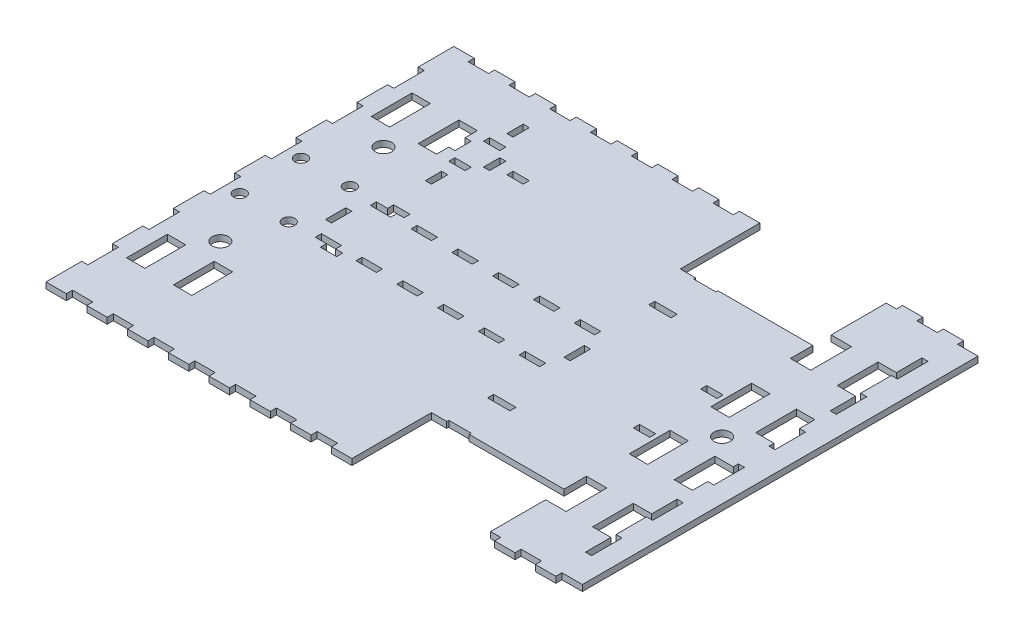
SolidWorks part; units mm, degrees
ref_plane "Front Plane" through (0, 0, 0) normal (0, 0, 1) x (1, 0, 0)
ref_plane "Top Plane" through (0, 0, 0) normal (0, 1, 0) x (1, 0, 0)
ref_plane "Right Plane" through (0, 0, 0) normal (1, 0, 0) x (0, 0, -1)
sketch "Sketch3" plane through (0, 0, 0) normal (0, 1, 0) x (1, 0, 0)
  line L0 (0, 0) -> (-300, 0) construction
  line L1 (-300, -97) -> (-300, 97)
  line L2 (-290, 100) -> (-300, 100)
  line L3 (-290, 97) -> (-290, 100)
  line L4 (-280, 97) -> (-290, 97)
  line L5 (-300, 100) -> (-300, 97)
  line L6 (-270, 100) -> (-280, 100)
  line L7 (-270, 97) -> (-270, 100)
  line L8 (-260, 97) -> (-270, 97)
  line L9 (-280, 100) -> (-280, 97)
  line L10 (-250, 100) -> (-260, 100)
  line L11 (-250, 97) -> (-250, 100)
  line L12 (-240, 97) -> (-250, 97)
  line L13 (-260, 100) -> (-260, 97)
  line L14 (-150, -100) -> (-150, 100) construction
  line L15 (-230, 100) -> (-240, 100)
  line L16 (-230, 97) -> (-230, 100)
  line L17 (-220, 97) -> (-230, 97)
  line L18 (-240, 100) -> (-240, 97)
  line L19 (-210, 100) -> (-220, 100)
  line L20 (-210, 97) -> (-210, 100)
  line L21 (-200, 97) -> (-210, 97)
  line L22 (-40, 97) -> (-40, -97)
  line L23 (-50, 37.5) -> (-53, 37.5)
  line L24 (-50, 7.5) -> (-53, 7.5)
  line L25 (-50, -45.947) -> (-50, 45.947) construction
  line L26 (-247, 37.5) -> (-250, 37.5) construction
  line L27 (-247, 7.5) -> (-250, 7.5) construction
  line L28 (-247, 48.5) -> (-247, -48.5) construction
  line L29 (-247, 48.5) -> (-223, 48.5) construction
  line L30 (-223, 48.5) -> (-223, -48.5) construction
  line L31 (-210, 15) -> (-90, 15) construction
  line L32 (-90, 15) -> (-90, 5) construction
  line L33 (-50, 7.5) -> (-50, 22.5)
  line L34 (-220, 100) -> (-220, 97)
  line L35 (-190, 100) -> (-200, 100)
  line L36 (-190, 97) -> (-190, 100)
  line L37 (-180, 97) -> (-190, 97)
  line L38 (-200, 100) -> (-200, 97)
  line L39 (-170, 100) -> (-180, 100)
  line L40 (-170, 97) -> (-170, 100)
  line L41 (-160, 97) -> (-170, 97)
  line L42 (-180, 100) -> (-180, 97)
  line L43 (-150, 100) -> (-160, 100)
  line L44 (-150, 97) -> (-150, 100)
  line L45 (-140, 97) -> (-150, 97)
  line L46 (-160, 100) -> (-160, 97)
  line L47 (-130, 100) -> (-140, 100)
  line L48 (-130, 97) -> (-130, 100)
  line L49 (-120, 97) -> (-130, 97)
  line L50 (-140, 100) -> (-140, 97)
  line L51 (-110, 100) -> (-120, 100)
  line L52 (-110, 97) -> (-110, 100)
  line L53 (-100, 97) -> (-110, 97)
  line L54 (-120, 100) -> (-120, 97)
  line L55 (-90, 100) -> (-100, 100)
  line L56 (-90, 97) -> (-90, 100)
  line L57 (-80, 97) -> (-90, 97)
  line L58 (-100, 100) -> (-100, 97)
  line L59 (-70, 100) -> (-80, 100)
  line L60 (-70, 97) -> (-70, 100)
  line L61 (-60, 97) -> (-70, 97)
  line L62 (-80, 100) -> (-80, 97)
  line L63 (-50, 100) -> (-60, 100)
  line L64 (-50, 97) -> (-50, 100)
  line L65 (-40, 97) -> (-50, 97)
  line L66 (-60, 100) -> (-60, 97)
  line L67 (-50, 22.5) -> (-53, 22.5)
  line L68 (-210, -15) -> (-90, -15) construction
  line L69 (-53, 7.5) -> (-53, 22.5)
  line L70 (-50, 37.5) -> (-50, 52.5)
  line L71 (-50, 52.5) -> (-53, 52.5)
  line L72 (-53, 37.5) -> (-53, 52.5)
  line L73 (-50, 67.5) -> (-53, 67.5)
  line L74 (-50, 67.5) -> (-50, 82.5)
  line L75 (-50, 82.5) -> (-53, 82.5)
  line L76 (-60, -100) -> (-60, -97)
  line L77 (-40, -97) -> (-50, -97)
  line L78 (-50, -97) -> (-50, -100)
  line L79 (-50, -100) -> (-60, -100)
  line L80 (-80, -100) -> (-80, -97)
  line L81 (-60, -97) -> (-70, -97)
  line L82 (-70, -97) -> (-70, -100)
  line L83 (-70, -100) -> (-80, -100)
  line L84 (-100, -100) -> (-100, -97)
  line L85 (-80, -97) -> (-90, -97)
  line L86 (-90, -97) -> (-90, -100)
  line L87 (-90, -100) -> (-100, -100)
  line L88 (-120, -100) -> (-120, -97)
  line L89 (-100, -97) -> (-110, -97)
  line L90 (-110, -97) -> (-110, -100)
  line L91 (-110, -100) -> (-120, -100)
  line L92 (-140, -100) -> (-140, -97)
  line L93 (-120, -97) -> (-130, -97)
  line L94 (-130, -97) -> (-130, -100)
  line L95 (-130, -100) -> (-140, -100)
  line L96 (-160, -100) -> (-160, -97)
  line L97 (-140, -97) -> (-150, -97)
  line L98 (-150, -97) -> (-150, -100)
  line L99 (-150, -100) -> (-160, -100)
  line L100 (-180, -100) -> (-180, -97)
  line L101 (-160, -97) -> (-170, -97)
  line L102 (-170, -97) -> (-170, -100)
  line L103 (-170, -100) -> (-180, -100)
  line L104 (-200, -100) -> (-200, -97)
  line L105 (-180, -97) -> (-190, -97)
  line L106 (-190, -97) -> (-190, -100)
  line L107 (-190, -100) -> (-200, -100)
  line L108 (-247, -48.5) -> (-223, -48.5) construction
  line L109 (-247, 7.5) -> (-247, 22.5) construction
  line L110 (-220, -100) -> (-220, -97)
  line L111 (-53, 67.5) -> (-53, 82.5)
  line L112 (-53, -67.5) -> (-53, -82.5)
  line L113 (-50, -82.5) -> (-53, -82.5)
  line L114 (-200, -97) -> (-210, -97)
  line L115 (-210, -97) -> (-210, -100)
  line L116 (-210, -100) -> (-220, -100)
  line L117 (-240, -100) -> (-240, -97)
  line L118 (-220, -97) -> (-230, -97)
  line L119 (-230, -97) -> (-230, -100)
  line L120 (-230, -100) -> (-240, -100)
  line L121 (-50, -67.5) -> (-50, -82.5)
  line L122 (-260, -100) -> (-260, -97)
  line L123 (-240, -97) -> (-250, -97)
  line L124 (-250, -97) -> (-250, -100)
  line L125 (-250, -100) -> (-260, -100)
  line L126 (-280, -100) -> (-280, -97)
  line L127 (-260, -97) -> (-270, -97)
  line L128 (-270, -97) -> (-270, -100)
  line L129 (-270, -100) -> (-280, -100)
  line L130 (-300, -100) -> (-300, -97)
  line L131 (-210, 15) -> (-210, -15) construction
  line L132 (-253, -15) -> (-243, -15)
  line L133 (-233, -15) -> (-223, -15)
  line L188 (-247, 22.5) -> (-250, 22.5) construction
  line L189 (-250, 7.5) -> (-250, 22.5) construction
  line L190 (-247, 37.5) -> (-247, 52.5) construction
  line L191 (-247, 52.5) -> (-250, 52.5) construction
  line L192 (-250, 37.5) -> (-250, 52.5) construction
  line L193 (-247, 67.5) -> (-250, 67.5) construction
  line L194 (-247, 67.5) -> (-247, 82.5) construction
  line L195 (-247, 82.5) -> (-250, 82.5) construction
  line L196 (-250, 67.5) -> (-250, 82.5) construction
  line L197 (-250, -67.5) -> (-250, -82.5) construction
  line L198 (-247, -82.5) -> (-250, -82.5) construction
  line L199 (-247, -67.5) -> (-247, -82.5) construction
  line L200 (-247, -67.5) -> (-250, -67.5) construction
  line L201 (-250, -37.5) -> (-250, -52.5) construction
  line L202 (-247, -52.5) -> (-250, -52.5) construction
  line L203 (-247, -37.5) -> (-247, -52.5) construction
  line L204 (-250, -7.5) -> (-250, -22.5) construction
  line L205 (-247, -22.5) -> (-250, -22.5) construction
  line L206 (-247, -7.5) -> (-247, -22.5) construction
  line L207 (-247, -7.5) -> (-250, -7.5) construction
  line L208 (-247, -37.5) -> (-250, -37.5) construction
  line L209 (-50, -67.5) -> (-53, -67.5)
  line L210 (-53, -37.5) -> (-53, -52.5)
  line L211 (-50, -52.5) -> (-53, -52.5)
  line L212 (-50, -37.5) -> (-50, -52.5)
  line L213 (-53, -7.5) -> (-53, -22.5)
  line L214 (-50, -22.5) -> (-53, -22.5)
  line L215 (-50, -7.5) -> (-50, -22.5)
  line L216 (-50, -7.5) -> (-53, -7.5)
  line L217 (-50, -37.5) -> (-53, -37.5)
  line L218 (-210, 0) -> (-258, 0)
  line L219 (-258, -5) -> (-255, -5)
  line L220 (-163, 15) -> (-173, 15)
  line L221 (-243, -12) -> (-243, -15)
  line L222 (-143, 15) -> (-143, 12)
  line L223 (-173, -15) -> (-173, -12)
  line L224 (-163, -15) -> (-173, -15)
  line L225 (-183, 12) -> (-183, 15)
  line L226 (-153, 15) -> (-153, 12)
  line L227 (-163, -12) -> (-163, -15)
  line L228 (-243, -12) -> (-253, -12)
  line L229 (-193, -15) -> (-193, -12)
  line L230 (-258, 5) -> (-255, 5)
  line L231 (-280, -97) -> (-290, -97)
  line L232 (-290, -97) -> (-290, -100)
  line L233 (-290, -100) -> (-300, -100)
  line L234 (-143, 15) -> (-153, 15)
  line L235 (-203, -12) -> (-213, -12)
  line L236 (-213, -15) -> (-213, -12)
  line L237 (-233, -15) -> (-233, -12)
  line L238 (-138, 5) -> (-141, 5)
  line L239 (-243, 12) -> (-243, 15)
  line L240 (-223, 12) -> (-223, 15)
  line L241 (-203, 12) -> (-213, 12)
  line L242 (-153, -15) -> (-153, -12)
  line L243 (-253, 15) -> (-253, 12)
  line L244 (-163, 12) -> (-163, 15)
  line L245 (-141, 5) -> (-141, -5)
  line L246 (-143, -15) -> (-143, -12)
  line L247 (-223, -12) -> (-233, -12)
  line L248 (-258, 15) -> (-258, -15) construction
  line L249 (-233, 15) -> (-233, 12)
  line L250 (-223, 15) -> (-233, 15)
  line L251 (-138, -5) -> (-141, -5)
  line L252 (-183, -15) -> (-193, -15)
  line L253 (-203, 15) -> (-213, 15)
  line L254 (-138, 5) -> (-138, -5)
  line L255 (-258, -15) -> (-138, -15) construction
  line L256 (-255, 5) -> (-255, -5)
  line L257 (-258, 5) -> (-258, -5)
  line L258 (-258, 15) -> (-138, 15) construction
  line L259 (-193, 15) -> (-193, 12)
  line L260 (-163, 12) -> (-173, 12)
  line L261 (-203, -15) -> (-213, -15)
  line L262 (-243, 12) -> (-253, 12)
  line L263 (-183, 15) -> (-193, 15)
  line L264 (-143, 12) -> (-153, 12)
  line L265 (-243, 15) -> (-253, 15)
  line L266 (-213, 15) -> (-213, 12)
  line L267 (-173, 15) -> (-173, 12)
  line L268 (-223, -12) -> (-223, -15)
  line L269 (-143, -12) -> (-153, -12)
  line L270 (-143, -15) -> (-153, -15)
  line L271 (-183, -12) -> (-193, -12)
  line L272 (-203, -12) -> (-203, -15)
  line L273 (-203, 12) -> (-203, 15)
  line L274 (-183, -12) -> (-183, -15)
  line L275 (-253, -15) -> (-253, -12)
  line L276 (-223, 12) -> (-233, 12)
  line L277 (-183, 12) -> (-193, 12)
  line L278 (-163, -12) -> (-173, -12)
  circle A0 centre (-290, 15) radius 3
  circle A1 centre (-266, 15) radius 3
  circle A2 centre (-266, -15) radius 3
  circle A3 centre (-290, -15) radius 3
  point P31 (-250, 36)
  point P80 (-91.5, 0)
  point P82 (-150, 0)
  point P126 (-223, 0)
  point P128 (-250, 18)
  point P129 (-50, 0)
  point P150 (-150, -15)
  point P151 (-150, 15)
  point P183 (-208.5, 0)
  point P212 (-223, 18)
  point P218 (-223, 36)
  point P235 (-198, -15)
  point P236 (-198, 15)
  dimension "D17" = 6
  dimension "D18" = 6
  dimension "D1" = 300
  dimension "D4" = 7.5
  dimension "D5" = 100
  dimension "D6" = 97
  dimension "D7" = 15
  dimension "D8" = 97
  dimension "D9" = 3
  dimension "D10" = 3
  dimension "D11" = 48.5
  dimension "D12" = 24
  dimension "D13" = 60
  dimension "D14" = 15
  dimension "D15" = 24
  dimension "D16" = 15
  dimension "D19" = 194
  dimension "D20" = 10
  dimension "D21" = 3
  dimension "D22" = 7.5
  dimension "D23" = 15
  dimension "D24" = 3
  dimension "D25" = 3
  dimension "D26" = 48
  dimension "D31" = 10
  dimension "D36" = 3
extrude "Boss-Extrude1" add sketch "Sketch3" along normal blind 3 contours L1 L116 L115 L107 L106 L83 L82 L79 L95 L98 L99 L91 L90 L86 region at (-170.2364, 0, 0)
sketch "Sketch5" plane through (0, 3, 0) normal (0, 1, 0) x (1, 0, 0)
  line L0 (-85, 0) -> (-85, 61) construction
  line L1 (-137, -60) -> (-137, -41)
  line L2 (-85, 61) -> (-131.5, 61)
  line L3 (-85, 61) -> (-85, 97)
  line L4 (-85, 97) -> (-150, 97)
  line L5 (-150, 61) -> (-150, 97)
  line L7 (-110, 100) -> (-120, 100) construction
  line L8 (-85, 0) -> (-300, 0) construction
  line L9 (-300, 100) -> (-300, -100) construction
  line L10 (-150, -61) -> (-150, -97)
  line L11 (-85, -97) -> (-150, -97)
  line L12 (-85, -61) -> (-85, -97)
  line L13 (-85, -61) -> (-131.5, -61)
  line L14 (-117.5, -61) -> (-117.5, -41) construction
  line L15 (-117.5, -41) -> (-131.5, -41) construction
  line L16 (-131.5, -41) -> (-131.5, -38)
  line L17 (-131.5, -38) -> (-142.5, -38)
  line L18 (-142.5, -38) -> (-142.5, -41)
  line L19 (-142.5, -41) -> (-131.5, -41)
  line L20 (-131.5, -61) -> (-131.5, -60)
  line L21 (-131.5, -60) -> (-142.5, -60)
  line L22 (-142.5, -60) -> (-142.5, -61)
  line L23 (-142.5, -61) -> (-150, -61)
  line L24 (-117.5, 41) -> (-131.5, 41) construction
  line L25 (-117.5, 61) -> (-117.5, 41) construction
  line L26 (-142.5, 60) -> (-142.5, 61)
  line L27 (-131.5, 60) -> (-142.5, 60)
  line L28 (-131.5, 61) -> (-131.5, 60)
  line L29 (-142.5, 41) -> (-131.5, 41)
  line L30 (-142.5, 38) -> (-142.5, 41)
  line L31 (-131.5, 38) -> (-142.5, 38)
  line L32 (-131.5, 41) -> (-131.5, 38)
  line L33 (-142.5, 61) -> (-150, 61)
  dimension "D1" = 19
  dimension "D2" = 36
  dimension "D3" = 3
  dimension "D5" = 14
  dimension "D6" = 3
  dimension "D7" = 11
  dimension "D9" = 1
extrude "Cut-Extrude2" cut sketch "Sketch5" against normal blind 10 contours L5 L2 L3 L4 | L12 L13 L10 L11 | L31 L30 L29 L32 | L17 L18 L19 L16 region at (-117.5912, 3, 78.9134) region at (-117.5912, 3, -78.9134) body kept at (-300, 0, -100)
sketch "Croquis1" plane through (0, 3, 0) normal (0, 1, 0) x (1, 0, 0)
  line L0 (-300, -67.5) -> (-300, -82.5)
  line L25 (-300, 100) -> (-300, -100) construction
  line L26 (-300, 37.5) -> (-300, 52.5)
  line L27 (-297, 37.5) -> (-300, 37.5)
  line L28 (-297, 7.5) -> (-300, 7.5)
  line L29 (-300, -7.5) -> (-297, -7.5)
  line L30 (-297, -22.5) -> (-300, -22.5)
  line L31 (-297, -7.5) -> (-297, -22.5)
  line L32 (-297, 82.5) -> (-297, 67.5)
  line L33 (-300, -22.5) -> (-300, -7.5)
  line L34 (-297, -37.5) -> (-297, -52.5)
  line L35 (-297, 67.5) -> (-300, 67.5)
  line L36 (-300, 67.5) -> (-300, 82.5)
  line L37 (-297, 52.5) -> (-297, 37.5)
  line L38 (-300, 22.5) -> (-297, 22.5)
  line L39 (-300, -37.5) -> (-297, -37.5)
  line L40 (-297, -52.5) -> (-300, -52.5)
  line L41 (-300, 52.5) -> (-297, 52.5)
  line L42 (-300, -52.5) -> (-300, -37.5)
  line L43 (-300, 82.5) -> (-297, 82.5)
  line L44 (-297, 22.5) -> (-297, 7.5)
  line L45 (-300, 7.5) -> (-300, 22.5)
  line L46 (-300, -67.5) -> (-297, -67.5)
  line L47 (-297, -67.5) -> (-297, -82.5)
  line L48 (-297, -82.5) -> (-300, -82.5)
  dimension "D1" = 15
  dimension "D2" = 15
extrude "Cortar-Extruir1" cut sketch "Croquis1" against normal blind 10
sketch "Croquis2" plane through (0, 3, 0) normal (0, 1, 0) x (1, 0, 0)
  line L0 (-40, 0) -> (-53, 0) construction
  line L1 (-40, 97) -> (-40, -97) construction
  line L2 (-53, 10) -> (-53, -10) construction
  line L3 (-53, -7.5) -> (-53, -22.5) construction
  line L4 (-53, -10) -> (-62, -10)
  line L5 (-62, -10) -> (-62, -30)
  line L6 (-62, -30) -> (-53, -30)
  line L7 (-53, -30) -> (-53, -10)
  line L8 (-53, -30) -> (-53, -50) construction
  line L9 (-53, -37.5) -> (-53, -52.5) construction
  line L10 (-53, -50) -> (-62, -50)
  line L11 (-62, -50) -> (-62, -70)
  line L12 (-62, -70) -> (-53, -70)
  line L13 (-53, -67.5) -> (-53, -82.5) construction
  line L14 (-53, -70) -> (-53, -50)
  line L15 (-53, 30) -> (-53, 50) construction
  line L16 (-53, 70) -> (-53, 50)
  line L17 (-62, 70) -> (-53, 70)
  line L18 (-62, 50) -> (-62, 70)
  line L19 (-53, 50) -> (-62, 50)
  line L20 (-53, 30) -> (-53, 10)
  line L21 (-62, 30) -> (-53, 30)
  line L22 (-62, 10) -> (-62, 30)
  line L23 (-53, 10) -> (-62, 10)
  line L24 (-62, 70) -> (-75, 70) construction
  line L25 (-75, 70) -> (-85, 70)
  line L26 (-75, 70) -> (-75, 50)
  line L27 (-75, 50) -> (-85, 50)
  line L28 (-85, 50) -> (-85, 70)
  line L29 (-75, 30) -> (-84, 30)
  line L30 (-84, 30) -> (-84, 10)
  line L31 (-84, 10) -> (-75, 10)
  line L32 (-75, 10) -> (-75, 30)
  line L33 (-75, -10) -> (-84, -10)
  line L34 (-84, -10) -> (-84, -30)
  line L35 (-84, -30) -> (-75, -30)
  line L36 (-75, -30) -> (-75, -10)
  line L37 (-75, -50) -> (-85, -50)
  line L38 (-85, -50) -> (-85, -70)
  line L39 (-85, -70) -> (-75, -70)
  line L40 (-75, -70) -> (-75, -50)
  line L41 (-266, 15) -> (-243.49, 15) construction
  line L42 (-68.5, 0) -> (-53, 0) construction
  line L43 (-243.49, 18) -> (-247.49, 18)
  line L44 (-247.49, 18) -> (-247.49, 15)
  line L45 (-290.5, 30) -> (-290.5, 50) construction
  line L46 (-290.5, -30) -> (-290.5, -50) construction
  line L47 (-247.49, 15) -> (-239.49, 15)
  line L48 (-239.49, 15) -> (-239.49, 18)
  line L49 (-267.5, -70) -> (-267.5, -50)
  line L50 (-258.5, -70) -> (-267.5, -70)
  line L51 (-258.5, -50) -> (-258.5, -70)
  line L52 (-267.5, -50) -> (-258.5, -50)
  line L53 (-239.49, 18) -> (-243.49, 18)
  line L54 (-68.5, 0) -> (-86, 0) construction
  line L55 (-239.49, -18) -> (-243.49, -18)
  line L56 (-239.49, -15) -> (-239.49, -18)
  line L57 (-247.49, -15) -> (-239.49, -15)
  line L58 (-247.49, -18) -> (-247.49, -15)
  line L59 (-243.49, -18) -> (-247.49, -18)
  line L60 (-86, 0) -> (-86, 15) construction
  line L61 (-258.5, 50) -> (-258.5, 56)
  line L62 (-267.5, 50) -> (-258.5, 50)
  line L63 (-267.5, 70) -> (-267.5, 50)
  line L64 (-267.5, 70) -> (-258.5, 70)
  line L65 (-86, 15) -> (-94, 15)
  line L66 (-94, 15) -> (-94, 18)
  line L67 (-94, 18) -> (-86, 18)
  line L68 (-86, 18) -> (-86, 15)
  line L69 (-290.5, 50) -> (-281.5, 50)
  line L70 (-281.5, 50) -> (-281.5, 70)
  line L71 (-281.5, 70) -> (-290.5, 70)
  line L72 (-290.5, 70) -> (-290.5, 50)
  line L73 (-290.5, -70) -> (-290.5, -50)
  line L74 (-281.5, -70) -> (-290.5, -70)
  line L75 (-281.5, -50) -> (-281.5, -70)
  line L76 (-290.5, -50) -> (-281.5, -50)
  line L77 (-86, -18) -> (-86, -15)
  line L78 (-86, -15) -> (-94, -15)
  line L79 (-94, -15) -> (-94, -18)
  line L80 (-94, -18) -> (-86, -18)
  line L81 (-258.5, 64) -> (-258.5, 70)
  line L82 (-248.5, 50) -> (-248.5, 40) construction
  line L83 (-248.5, 70) -> (-248.5, 80) construction
  line L84 (-250, 40) -> (-250, 44)
  line L85 (-250, 44) -> (-247, 44)
  line L86 (-247, 44) -> (-247, 36)
  line L87 (-247, 36) -> (-250, 36)
  line L88 (-252.5, 50) -> (-244.5, 50)
  line L89 (-250, 36) -> (-250, 40)
  line L90 (-238.5, 60) -> (-228.5, 60) construction
  line L91 (-250, 80) -> (-250, 76)
  line L92 (-250, 76) -> (-247, 76)
  line L93 (-247, 76) -> (-247, 84)
  line L94 (-247, 84) -> (-250, 84)
  line L95 (-250, 84) -> (-250, 80)
  line L97 (-228.5, 61.5) -> (-232.5, 61.5)
  line L98 (-232.5, 61.5) -> (-232.5, 58.5)
  line L99 (-232.5, 58.5) -> (-224.5, 58.5)
  line L100 (-224.5, 58.5) -> (-224.5, 61.5)
  line L101 (-224.5, 61.5) -> (-228.5, 61.5)
  line L104 (-244.5, 53) -> (-244.5, 50)
  line L105 (-241.5, 56) -> (-238.5, 56)
  line L106 (-241.5, 64) -> (-238.5, 64)
  line L107 (-248.5, 97) -> (-248.5, 60) construction
  line L108 (-252.5, 70) -> (-244.5, 70)
  line L109 (-255.5, 56) -> (-255.5, 64)
  line L110 (-248.5, 53) -> (-252.5, 53)
  line L111 (-255.5, 64) -> (-258.5, 64)
  line L112 (-248.5, 70) -> (-248.5, 67) construction
  line L113 (-252.5, 53) -> (-252.5, 50)
  line L114 (-258.5, 60) -> (-255.5, 60) construction
  line L115 (-244.5, 67) -> (-252.5, 67)
  line L116 (-255.5, 56) -> (-258.5, 56)
  line L117 (-241.5, 56) -> (-241.5, 64)
  line L118 (-248.5, 50) -> (-248.5, 53) construction
  line L119 (-244.5, 67) -> (-244.5, 70)
  line L121 (-252.5, 67) -> (-252.5, 70)
  line L122 (-238.5, 64) -> (-238.5, 56)
  line L123 (-248.5, 53) -> (-244.5, 53)
  circle A0 centre (-68.5, 0) radius 4
  circle A3 centre (-274.5, -40) radius 4
  circle A4 centre (-274.5, 40) radius 4
  dimension "D8" = 8
  dimension "D11" = 8
  dimension "D12" = 8
  dimension "D1" = 10
  dimension "D2" = 9
  dimension "D3" = 20
  dimension "D4" = 20
  dimension "D5" = 13
  dimension "D6" = 10
  dimension "D7" = 20
  dimension "D9" = 14
  dimension "D10" = 22.51
  dimension "D13" = 3
  dimension "D14" = 4
  dimension "D15" = 8
  dimension "D16" = 9
  dimension "D17" = 13
  dimension "D18" = 9
  dimension "D19" = 13
  dimension "D20" = 9
  dimension "D21" = 13
  dimension "D22" = 10
  dimension "D23" = 9
  dimension "D24" = 9
  dimension "D25" = 9
  dimension "D26" = 9
  dimension "D27" = 14
  dimension "D28" = 17.5
  dimension "D29" = 15.5
  dimension "D30" = 15
  dimension "D31" = 8
  dimension "D32" = 3
  dimension "D33" = 3
  dimension "D34" = 4
  dimension "D35" = 10
  dimension "D36" = 1.5
  dimension "D37" = 4
  dimension "D38" = 3
  dimension "D39" = 8
  dimension "D40" = 10
  dimension "D41" = 1.5
  dimension "D42" = 3
  dimension "D43" = 4
  dimension "D44" = 4
  dimension "D45" = 3
  dimension "D46" = 4
  dimension "D47" = 4
  dimension "D48" = 8
  dimension "D49" = 10
  dimension "D50" = 1.5
  dimension "D51" = 4
  dimension "D52" = 3
  dimension "D53" = 8
extrude "Cortar-Extruir2" cut sketch "Croquis2" against normal blind 10
